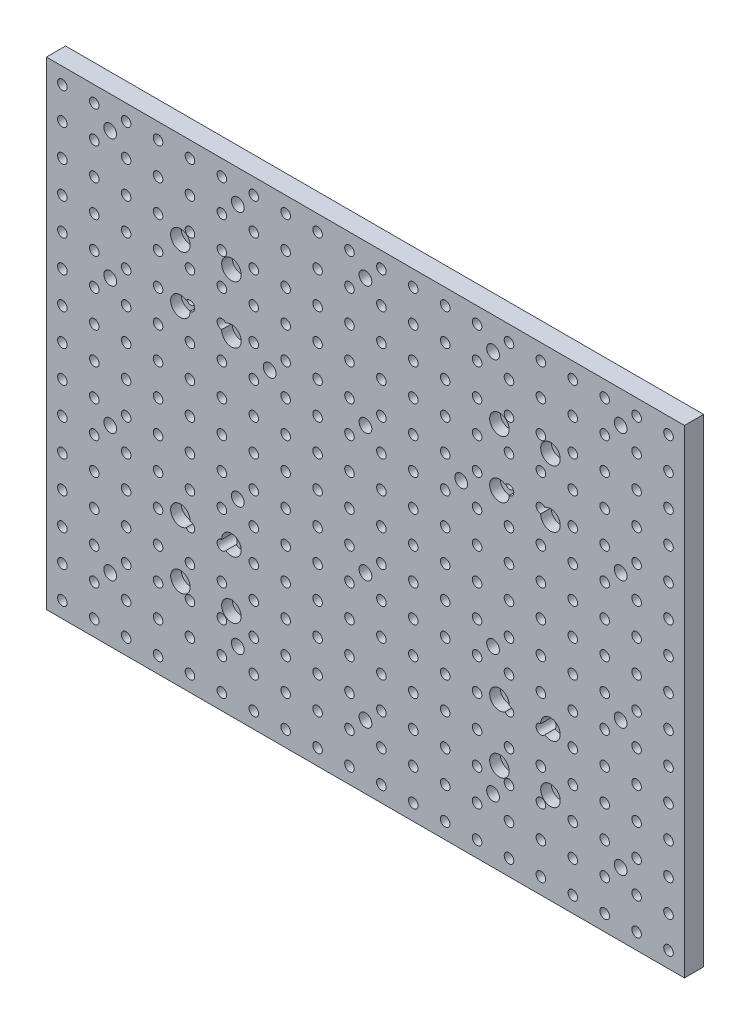
SolidWorks part; units mm, degrees
ref_plane "Front Plane" through (0, 0, 0) normal (0, 0, 1) x (1, 0, 0)
ref_plane "Top Plane" through (0, 0, 0) normal (0, 1, 0) x (1, 0, 0)
ref_plane "Right Plane" through (0, 0, 0) normal (1, 0, 0) x (0, 0, -1)
sketch "Sketch1" plane through (0, 0, 0) normal (0, 0, 1) x (1, 0, 0)
  line L1 (-200, 150) -> (200, 150)
  line L2 (-200, 150) -> (-200, -150)
  line L3 (-200, -150) -> (200, -150)
  line L4 (200, 150) -> (200, -150)
  line L5 (0, -150) -> (0, 150) construction
  line L6 (-200, 0) -> (200, 0) construction
  point P0 (0, 0)
  dimension "D1" = 300
  dimension "D2" = 400
extrude "Boss-Extrude1" add sketch "Sketch1" along normal blind 12
sketch "Sketch3" plane through (0, 0, 12) normal (0, 0, 1) x (1, 0, 0)
  circle A0 centre (-116, 92.75) radius 5
  circle A1 centre (-84, 92.75) radius 5
  circle A2 centre (-116, 56.75) radius 5
  circle A3 centre (-84, 56.75) radius 5
  circle A4 centre (84, 92.75) radius 5
  circle A5 centre (116, 92.75) radius 5
  circle A6 centre (84, 56.75) radius 5
  circle A7 centre (116, 56.75) radius 5
  circle A8 centre (116, -56.75) radius 5
  circle A9 centre (84, -56.75) radius 5
  circle A10 centre (84, -92.75) radius 5
  circle A11 centre (116, -92.75) radius 5
  circle A12 centre (-84, -92.75) radius 5
  circle A13 centre (-116, -92.75) radius 5
  circle A14 centre (-116, -56.75) radius 5
  circle A15 centre (-84, -56.75) radius 5
hole_wizard "CBORE for M5 Hex Head Bolt1" positions "3DSketch2" profile "Sketch4" counterbore size "M5" standard "ANSI Metric"
sketch3d "3DSketch2"
  point P0 (-116, 92.75, 12)
  point P3 (-84, 92.75, 12)
  point P6 (-116, 56.75, 12)
  point P9 (-84, 56.75, 12)
  point P17 (-116, -56.75, 12)
  point P22 (-84, -56.75, 12)
  point P25 (-116, -92.75, 12)
  point P28 (-84, -92.75, 12)
  point P31 (116, -92.75, 12)
  point P34 (84, -92.75, 12)
  point P37 (84, -56.75, 12)
  point P40 (116, -56.75, 12)
  point P43 (84, 92.75, 12)
  point P46 (116, 92.75, 12)
  point P49 (84, 56.75, 12)
  point P52 (116, 56.75, 12)
sketch "Sketch4" plane through (-116, 92.75, 12) normal (1, 0, 0) x (0, -1, 0)
  line L0 (0, 0) -> (0, 30)
  line L1 (0, 30) -> (2.75, 28.3476)
  line L2 (2.75, 28.3476) -> (2.75, 6.58)
  line L3 (2.75, 6.58) -> (6.12, 6.58)
  line L4 (6.12, 6.58) -> (6.12, 0)
  line L5 (6.12, 0) -> (0, 0)
  line L10 (0, 30) -> (-2.75, 28.3476) construction
  line L11 (0, -6.35) -> (0, 107.95) construction
  dimension "Hole Dia." = 5.5
  dimension "Hole Depth" = 30
  dimension "C'Bore Dia." = 12.24
  dimension "C'Bore Depth" = 6.58
  dimension "Drill Angle" = 118
sketch "Sketch5" plane through (0, 0, 12) normal (0, 0, 1) x (1, 0, 0)
  line L0 (-190, 140) -> (-170, 140) construction
  line L1 (-190, 140) -> (-190, 120) construction
  circle A0 centre (-190, 140) radius 3
  circle A1 centre (-170, 140) radius 3
  circle A2 centre (-150, 140) radius 3
  circle A3 centre (-130, 140) radius 3
  circle A4 centre (-110, 140) radius 3
  circle A5 centre (-90, 140) radius 3
  circle A6 centre (-70, 140) radius 3
  circle A7 centre (-50, 140) radius 3
  circle A8 centre (-30, 140) radius 3
  circle A9 centre (-10, 140) radius 3
  circle A10 centre (10, 140) radius 3
  circle A11 centre (30, 140) radius 3
  circle A12 centre (50, 140) radius 3
  circle A13 centre (70, 140) radius 3
  circle A14 centre (90, 140) radius 3
  circle A15 centre (110, 140) radius 3
  circle A16 centre (130, 140) radius 3
  circle A17 centre (150, 140) radius 3
  circle A18 centre (170, 140) radius 3
  circle A19 centre (190, 140) radius 3
  circle A20 centre (-170, 120) radius 3
  circle A21 centre (-150, 120) radius 3
  circle A22 centre (-130, 120) radius 3
  circle A23 centre (-110, 120) radius 3
  circle A24 centre (-90, 120) radius 3
  circle A25 centre (-70, 120) radius 3
  circle A26 centre (-50, 120) radius 3
  circle A27 centre (-30, 120) radius 3
  circle A28 centre (-10, 120) radius 3
  circle A29 centre (10, 120) radius 3
  circle A30 centre (30, 120) radius 3
  circle A31 centre (50, 120) radius 3
  circle A32 centre (70, 120) radius 3
  circle A33 centre (90, 120) radius 3
  circle A34 centre (110, 120) radius 3
  circle A35 centre (130, 120) radius 3
  circle A36 centre (150, 120) radius 3
  circle A37 centre (170, 120) radius 3
  circle A38 centre (190, 120) radius 3
  circle A39 centre (-170, 100) radius 3
  circle A40 centre (-150, 100) radius 3
  circle A41 centre (-130, 100) radius 3
  circle A42 centre (-110, 100) radius 3
  circle A43 centre (-90, 100) radius 3
  circle A44 centre (-70, 100) radius 3
  circle A45 centre (-50, 100) radius 3
  circle A46 centre (-30, 100) radius 3
  circle A47 centre (-10, 100) radius 3
  circle A48 centre (10, 100) radius 3
  circle A49 centre (30, 100) radius 3
  circle A50 centre (50, 100) radius 3
  circle A51 centre (70, 100) radius 3
  circle A52 centre (90, 100) radius 3
  circle A53 centre (110, 100) radius 3
  circle A54 centre (130, 100) radius 3
  circle A55 centre (150, 100) radius 3
  circle A56 centre (170, 100) radius 3
  circle A57 centre (190, 100) radius 3
  circle A58 centre (-170, 80) radius 3
  circle A59 centre (-150, 80) radius 3
  circle A60 centre (-130, 80) radius 3
  circle A61 centre (-110, 80) radius 3
  circle A62 centre (-90, 80) radius 3
  circle A63 centre (-70, 80) radius 3
  circle A64 centre (-50, 80) radius 3
  circle A65 centre (-30, 80) radius 3
  circle A66 centre (-10, 80) radius 3
  circle A67 centre (10, 80) radius 3
  circle A68 centre (30, 80) radius 3
  circle A69 centre (50, 80) radius 3
  circle A70 centre (70, 80) radius 3
  circle A71 centre (90, 80) radius 3
  circle A72 centre (110, 80) radius 3
  circle A73 centre (130, 80) radius 3
  circle A74 centre (150, 80) radius 3
  circle A75 centre (170, 80) radius 3
  circle A76 centre (190, 80) radius 3
  circle A77 centre (-170, 60) radius 3
  circle A78 centre (-150, 60) radius 3
  circle A79 centre (-130, 60) radius 3
  circle A80 centre (-110, 60) radius 3
  circle A81 centre (-90, 60) radius 3
  circle A82 centre (-70, 60) radius 3
  circle A83 centre (-50, 60) radius 3
  circle A84 centre (-30, 60) radius 3
  circle A85 centre (-10, 60) radius 3
  circle A86 centre (10, 60) radius 3
  circle A87 centre (30, 60) radius 3
  circle A88 centre (50, 60) radius 3
  circle A89 centre (70, 60) radius 3
  circle A90 centre (90, 60) radius 3
  circle A91 centre (110, 60) radius 3
  circle A92 centre (130, 60) radius 3
  circle A93 centre (150, 60) radius 3
  circle A94 centre (170, 60) radius 3
  circle A95 centre (190, 60) radius 3
  circle A96 centre (-170, 40) radius 3
  circle A97 centre (-150, 40) radius 3
  circle A98 centre (-130, 40) radius 3
  circle A99 centre (-110, 40) radius 3
  circle A100 centre (-90, 40) radius 3
  circle A101 centre (-70, 40) radius 3
  circle A102 centre (-50, 40) radius 3
  circle A103 centre (-30, 40) radius 3
  circle A104 centre (-10, 40) radius 3
  circle A105 centre (10, 40) radius 3
  circle A106 centre (30, 40) radius 3
  circle A107 centre (50, 40) radius 3
  circle A108 centre (70, 40) radius 3
  circle A109 centre (90, 40) radius 3
  circle A110 centre (110, 40) radius 3
  circle A111 centre (130, 40) radius 3
  circle A112 centre (150, 40) radius 3
  circle A113 centre (170, 40) radius 3
  circle A114 centre (190, 40) radius 3
  circle A115 centre (-170, 20) radius 3
  circle A116 centre (-150, 20) radius 3
  circle A117 centre (-130, 20) radius 3
  circle A118 centre (-110, 20) radius 3
  circle A119 centre (-90, 20) radius 3
  circle A120 centre (-70, 20) radius 3
  circle A121 centre (-50, 20) radius 3
  circle A122 centre (-30, 20) radius 3
  circle A123 centre (-10, 20) radius 3
  circle A124 centre (10, 20) radius 3
  circle A125 centre (30, 20) radius 3
  circle A126 centre (50, 20) radius 3
  circle A127 centre (70, 20) radius 3
  circle A128 centre (90, 20) radius 3
  circle A129 centre (110, 20) radius 3
  circle A130 centre (130, 20) radius 3
  circle A131 centre (150, 20) radius 3
  circle A132 centre (170, 20) radius 3
  circle A133 centre (190, 20) radius 3
  circle A134 centre (-170, 0) radius 3
  circle A135 centre (-150, 0) radius 3
  circle A136 centre (-130, 0) radius 3
  circle A137 centre (-110, 0) radius 3
  circle A138 centre (-90, 0) radius 3
  circle A139 centre (-70, 0) radius 3
  circle A140 centre (-50, 0) radius 3
  circle A141 centre (-30, 0) radius 3
  circle A142 centre (-10, 0) radius 3
  circle A143 centre (10, 0) radius 3
  circle A144 centre (30, 0) radius 3
  circle A145 centre (50, 0) radius 3
  circle A146 centre (70, 0) radius 3
  circle A147 centre (90, 0) radius 3
  circle A148 centre (110, 0) radius 3
  circle A149 centre (130, 0) radius 3
  circle A150 centre (150, 0) radius 3
  circle A151 centre (170, 0) radius 3
  circle A152 centre (190, 0) radius 3
  circle A153 centre (-170, -20) radius 3
  circle A154 centre (-150, -20) radius 3
  circle A155 centre (-130, -20) radius 3
  circle A156 centre (-110, -20) radius 3
  circle A157 centre (-90, -20) radius 3
  circle A158 centre (-70, -20) radius 3
  circle A159 centre (-50, -20) radius 3
  circle A160 centre (-30, -20) radius 3
  circle A161 centre (-10, -20) radius 3
  circle A162 centre (10, -20) radius 3
  circle A163 centre (30, -20) radius 3
  circle A164 centre (50, -20) radius 3
  circle A165 centre (70, -20) radius 3
  circle A166 centre (90, -20) radius 3
  circle A167 centre (110, -20) radius 3
  circle A168 centre (130, -20) radius 3
  circle A169 centre (150, -20) radius 3
  circle A170 centre (170, -20) radius 3
  circle A171 centre (190, -20) radius 3
  circle A172 centre (-170, -40) radius 3
  circle A173 centre (-150, -40) radius 3
  circle A174 centre (-130, -40) radius 3
  circle A175 centre (-110, -40) radius 3
  circle A176 centre (-90, -40) radius 3
  circle A177 centre (-70, -40) radius 3
  circle A178 centre (-50, -40) radius 3
  circle A179 centre (-30, -40) radius 3
  circle A180 centre (-10, -40) radius 3
  circle A181 centre (10, -40) radius 3
  circle A182 centre (30, -40) radius 3
  circle A183 centre (50, -40) radius 3
  circle A184 centre (70, -40) radius 3
  circle A185 centre (90, -40) radius 3
  circle A186 centre (110, -40) radius 3
  circle A187 centre (130, -40) radius 3
  circle A188 centre (150, -40) radius 3
  circle A189 centre (170, -40) radius 3
  circle A190 centre (190, -40) radius 3
  circle A191 centre (-170, -60) radius 3
  circle A192 centre (-150, -60) radius 3
  circle A193 centre (-130, -60) radius 3
  circle A194 centre (-110, -60) radius 3
  circle A195 centre (-90, -60) radius 3
  circle A196 centre (-70, -60) radius 3
  circle A197 centre (-50, -60) radius 3
  circle A198 centre (-30, -60) radius 3
  circle A199 centre (-10, -60) radius 3
  circle A200 centre (10, -60) radius 3
  circle A201 centre (30, -60) radius 3
  circle A202 centre (50, -60) radius 3
  circle A203 centre (70, -60) radius 3
  circle A204 centre (90, -60) radius 3
  circle A205 centre (110, -60) radius 3
  circle A206 centre (130, -60) radius 3
  circle A207 centre (150, -60) radius 3
  circle A208 centre (170, -60) radius 3
  circle A209 centre (190, -60) radius 3
  circle A210 centre (-170, -80) radius 3
  circle A211 centre (-150, -80) radius 3
  circle A212 centre (-130, -80) radius 3
  circle A213 centre (-110, -80) radius 3
  circle A214 centre (-90, -80) radius 3
  circle A215 centre (-70, -80) radius 3
  circle A216 centre (-50, -80) radius 3
  circle A217 centre (-30, -80) radius 3
  circle A218 centre (-10, -80) radius 3
  circle A219 centre (10, -80) radius 3
  circle A220 centre (30, -80) radius 3
  circle A221 centre (50, -80) radius 3
  circle A222 centre (70, -80) radius 3
  circle A223 centre (90, -80) radius 3
  circle A224 centre (110, -80) radius 3
  circle A225 centre (130, -80) radius 3
  circle A226 centre (150, -80) radius 3
  circle A227 centre (170, -80) radius 3
  circle A228 centre (190, -80) radius 3
  circle A229 centre (-170, -100) radius 3
  circle A230 centre (-150, -100) radius 3
  circle A231 centre (-130, -100) radius 3
  circle A232 centre (-110, -100) radius 3
  circle A233 centre (-90, -100) radius 3
  circle A234 centre (-70, -100) radius 3
  circle A235 centre (-50, -100) radius 3
  circle A236 centre (-30, -100) radius 3
  circle A237 centre (-10, -100) radius 3
  circle A238 centre (10, -100) radius 3
  circle A239 centre (30, -100) radius 3
  circle A240 centre (50, -100) radius 3
  circle A241 centre (70, -100) radius 3
  circle A242 centre (90, -100) radius 3
  circle A243 centre (110, -100) radius 3
  circle A244 centre (130, -100) radius 3
  circle A245 centre (150, -100) radius 3
  circle A246 centre (170, -100) radius 3
  circle A247 centre (190, -100) radius 3
  circle A248 centre (-170, -120) radius 3
  circle A249 centre (-150, -120) radius 3
  circle A250 centre (-130, -120) radius 3
  circle A251 centre (-110, -120) radius 3
  circle A252 centre (-90, -120) radius 3
  circle A253 centre (-70, -120) radius 3
  circle A254 centre (-50, -120) radius 3
  circle A255 centre (-30, -120) radius 3
  circle A256 centre (-10, -120) radius 3
  circle A257 centre (10, -120) radius 3
  circle A258 centre (30, -120) radius 3
  circle A259 centre (50, -120) radius 3
  circle A260 centre (70, -120) radius 3
  circle A261 centre (90, -120) radius 3
  circle A262 centre (110, -120) radius 3
  circle A263 centre (130, -120) radius 3
  circle A264 centre (150, -120) radius 3
  circle A265 centre (170, -120) radius 3
  circle A266 centre (190, -120) radius 3
  circle A267 centre (-170, -140) radius 3
  circle A268 centre (-150, -140) radius 3
  circle A269 centre (-130, -140) radius 3
  circle A270 centre (-110, -140) radius 3
  circle A271 centre (-90, -140) radius 3
  circle A272 centre (-70, -140) radius 3
  circle A273 centre (-50, -140) radius 3
  circle A274 centre (-30, -140) radius 3
  circle A275 centre (-10, -140) radius 3
  circle A276 centre (10, -140) radius 3
  circle A277 centre (30, -140) radius 3
  circle A278 centre (50, -140) radius 3
  circle A279 centre (70, -140) radius 3
  circle A280 centre (90, -140) radius 3
  circle A281 centre (110, -140) radius 3
  circle A282 centre (130, -140) radius 3
  circle A283 centre (150, -140) radius 3
  circle A284 centre (170, -140) radius 3
  circle A285 centre (190, -140) radius 3
  circle A286 centre (-190, 120) radius 3
  circle A287 centre (-190, 100) radius 3
  circle A288 centre (-190, 80) radius 3
  circle A289 centre (-190, 60) radius 3
  circle A290 centre (-190, 40) radius 3
  circle A291 centre (-190, 20) radius 3
  circle A292 centre (-190, 0) radius 3
  circle A293 centre (-190, -20) radius 3
  circle A294 centre (-190, -40) radius 3
  circle A295 centre (-190, -60) radius 3
  circle A296 centre (-190, -80) radius 3
  circle A297 centre (-190, -100) radius 3
  circle A298 centre (-190, -120) radius 3
  circle A299 centre (-190, -140) radius 3
  dimension "D1" = 20
  dimension "D3" = 20
  dimension "D4" = 20
  dimension "D2" = 15
extrude "Cut-Extrude1" cut sketch "Sketch5" against normal through all
sketch "Sketch6" plane through (0, 0, 12) normal (0, 0, 1) x (1, 0, 0)
  line L0 (-160, 130) -> (-80, 130) construction
  circle A0 centre (-160, 130) radius 4
  circle A1 centre (-80, 130) radius 4
  circle A2 centre (0, 130) radius 4
  circle A3 centre (80, 130) radius 4
  circle A4 centre (160, 130) radius 4
  circle A25 centre (-160, 50) radius 4
  circle A27 centre (0, 50) radius 4
  circle A29 centre (160, 50) radius 4
  circle A30 centre (-160, -30) radius 4
  circle A31 centre (-80, -30) radius 4
  circle A32 centre (0, -30) radius 4
  circle A33 centre (80, -30) radius 4
  circle A34 centre (160, -30) radius 4
  circle A35 centre (-160, -110) radius 4
  circle A36 centre (-80, -110) radius 4
  circle A37 centre (0, -110) radius 4
  circle A38 centre (80, -110) radius 4
  circle A39 centre (160, -110) radius 4
  circle A40 centre (-60, 50) radius 4
  circle A41 centre (-80, 50) radius 4
  circle A42 centre (60, 50) radius 4
  circle A43 centre (80, 50) radius 4
  dimension "D1" = 5
  dimension "D3" = 80
  dimension "D2" = 4
extrude "Cut-Extrude2" cut sketch "Sketch6" against normal through all
